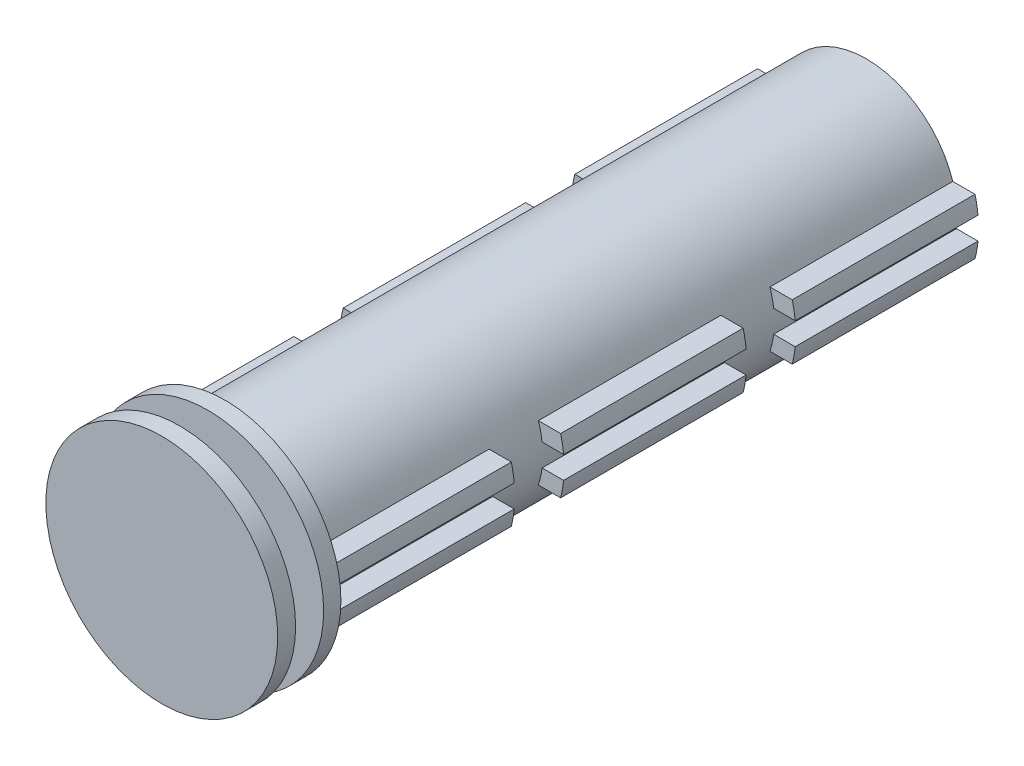
SolidWorks part; units mm, degrees
material "Nylon 101"
ref_plane "Front Plane" through (0, 0, 0) normal (0, 0, 1) x (1, 0, 0)
ref_plane "Top Plane" through (0, 0, 0) normal (0, 1, 0) x (1, 0, 0)
ref_plane "Right Plane" through (0, 0, 0) normal (1, 0, 0) x (0, 0, -1)
sketch "Sketch1" plane through (0, 0, 0) normal (0, 0, 1) x (1, 0, 0)
  circle A0 centre (-78.5195, 2.7413) radius 9.3536
extrude "Boss-Extrude1" add sketch "Sketch1" along normal blind 66.04 contours A0
sketch "Sketch7" plane through (0, 0, 66.04) normal (0, 0, 1) x (1, 0, 0)
  circle A0 centre (-78.5195, 2.7413) radius 11.938
extrude "Boss-Extrude4" add sketch "Sketch7" along normal blind 1.778
ref_plane "Plane2" through (-69.85, 0, 0) normal (1, 0, 0) x (0, 0, -1)
sketch "Sketch12" plane through (-69.85, 0, 0) normal (1, 0, 0) x (0, 0, -1)
  line L0 (-66.04, 5.6115) -> (-66.04, 3.897)
  line L1 (-66.04, 1.5788) -> (-66.04, -0.1289)
  line L2 (0, 1.5856) -> (-18.8248, 1.5856)
  line L3 (-18.8248, 1.5856) -> (-18.8248, -0.1289)
  line L4 (-18.8248, -0.1289) -> (0, -0.1289)
  line L5 (0, -0.1289) -> (0, 1.5856)
  line L6 (0, 5.6115) -> (0, 3.897)
  line L7 (-18.8248, 5.6115) -> (0, 5.6115)
  line L8 (-18.8248, 3.897) -> (-18.8248, 5.6115)
  line L9 (0, 3.897) -> (-18.8248, 3.897)
  line L10 (-23.876, 1.5856) -> (-42.672, 1.5856)
  line L11 (-23.876, -0.1289) -> (-23.876, 1.5856)
  line L12 (-42.672, 1.5856) -> (-42.672, -0.1289)
  line L13 (-42.672, 5.6115) -> (-23.876, 5.6115)
  line L14 (-42.672, 3.897) -> (-42.672, 5.6115)
  line L15 (-23.876, 3.897) -> (-42.672, 3.897)
  line L16 (-42.672, -0.1289) -> (-23.876, -0.1289)
  line L17 (-23.876, 5.6115) -> (-23.876, 3.897)
  line L18 (-47.752, 5.6115) -> (-47.752, 3.897)
  line L19 (-66.04, -0.1289) -> (-47.752, -0.1289)
  line L20 (-66.04, 5.6115) -> (-47.752, 5.6115)
  line L21 (-47.752, -0.1289) -> (-47.752, 1.5788)
  line L22 (-47.752, 3.897) -> (-66.04, 3.897)
  line L23 (-47.752, 1.5788) -> (-66.04, 1.5788)
sketch "Sketch14" plane through (0, 0, 0) normal (0, 0, -1) x (-1, 0, 0)
  circle A0 centre (78.5195, 2.7413) radius 7.7153
extrude "Cut-Extrude1" cut sketch "Sketch14" against normal blind 66.04 contours A0
extrude "Boss-Extrude5" add sketch "Sketch12" along normal blind 2.8448 contours L9 L8 L7 L6 | L0 L22 L18 L20 | L13 L17 L15 L14 | L1 L19 L21 L23 | L10 L12 L16 L11 | L2 L3 L4 L5
sketch "Sketch17" plane through (0, 0, 0) normal (0, 0, -1) x (-1, 0, 0)
  line L0 (66.9625, -0.2507) -> (90.4575, 2.7413)
  line L1 (78.5195, -4.974) -> (78.5195, 6.6348)
  line L2 (69.85, 12.7127) -> (69.85, -12.7127) construction
  line L5 (66.9625, -0.2507) -> (66.9625, 9.1139)
  line L6 (10.2889, 0) -> (-10.2889, 0) construction
  line L9 (75.9795, -6.6123) -> (75.9795, -5.3423)
  line L11 (81.0595, -6.6123) -> (81.0595, -5.3423)
  line L12 (75.9795, -5.3423) -> (81.0595, -5.3423)
  line L13 (75.9795, -6.6123) -> (75.9795, -9.1523)
  line L14 (81.0595, -6.6123) -> (81.0595, -9.1523)
  line L15 (75.9795, -9.1523) -> (81.0595, -9.1523)
  circle A0 centre (78.5195, 2.7413) radius 11.938 construction
  circle A1 centre (78.5195, 2.7413) radius 11.938 construction
  circle A2 centre (78.5195, 2.7413) radius 7.7153 construction
  circle A3 centre (78.5195, 2.7413) radius 7.7153 construction
  arc M5 (69.6172, -0.1289) -> (69.6172, 5.6115) centre (78.5195, 2.7413) ccw
  dimension "D1" = 8.6695
  dimension "D2" = 8.6695
  dimension "D3" = 11.557
  dimension "D4" = 2.7281
ref_plane "Plane3" through (-78.5622, 0, 0) normal (1, 0, 0) x (0, 0, -1)
ref_plane "Plane4" through (-87.1982, 0, 0) normal (1, 0, 0) x (0, 0, -1)
mirror "Mirror2" about plane through (-78.5622, 0, 0) normal (1, 0, 0) of "Boss-Extrude5"
sketch "Sketch19" plane through (0, 0, 0) normal (0, 0, -1) x (-1, 0, 0)
  line L0 (67.0205, 3.897) -> (67.0052, 3.897)
  line L1 (67.0052, 3.897) -> (67.0052, 5.6115)
  line L2 (67.0052, 5.6115) -> (67.3246, 5.6115)
  line L3 (67.0052, 1.5856) -> (67.0205, 1.5856)
  line L5 (67.0052, 1.5856) -> (67.0052, -0.1289)
  line L7 (67.0052, -0.1289) -> (67.3246, -0.1289)
  line L14 (67.0052, 1.5856) -> (69.2377, 1.5856) construction
  line L19 (90.1192, 5.6115) -> (89.7144, 5.6115)
  line L20 (90.1192, 5.6115) -> (90.1192, 3.897)
  line L21 (90.1192, 3.897) -> (90.0186, 3.897)
  line L22 (89.7144, -0.1289) -> (90.1192, -0.1289)
  line L23 (90.1192, -0.1289) -> (90.1192, 1.5856)
  line L24 (90.1192, 1.5856) -> (90.0179, 1.5788)
  arc A0 (67.3246, 5.6115) -> (67.0205, 3.897) centre (78.5195, 2.7413) ccw
  arc A1 (67.0205, 1.5856) -> (67.3246, -0.1289) centre (78.5195, 2.7413) ccw
  arc A5 (67.3246, 5.6115) -> (67.0205, 3.897) centre (78.5195, 2.7413) ccw
  arc A9 (89.7144, 5.6115) -> (90.0186, 3.897) centre (78.5195, 2.7413) cw
  arc A12 (90.0179, 1.5788) -> (89.7144, -0.1289) centre (78.5195, 2.7413) cw
extrude "Cut-Extrude2" cut sketch "Sketch19" against normal blind 66.04 contours A0 L0 L1 L2 | L3 A1 L7 L5 | A9 L21 L20 L19 | L24 A12 L22 L23
sketch "Sketch21" plane through (0, 0, 67.818) normal (0, 0, 1) x (1, 0, 0)
  line L1 (-78.5622, -18.518) -> (-78.5622, 18.518) construction
  circle A1 centre (-78.5622, 2.7413) radius 7.3995
extrude "Boss-Extrude7" add sketch "Sketch21" along normal blind 2.8448
sketch "Sketch22" plane through (0, 0, 70.6628) normal (0, 0, 1) x (1, 0, 0)
  circle A0 centre (-78.5622, 2.7413) radius 11.938
extrude "Boss-Extrude8" add sketch "Sketch22" along normal blind 1.8415
ref_plane "Plane5" through (0, 2.728, 0) normal (0, 1, 0) x (1, 0, 0)
extrude "Cut-Extrude3" cut sketch "Sketch17" against normal blind 66.04 contours L12 L9 L11 M5 region at (-78.5195, -5.9239, 0)
